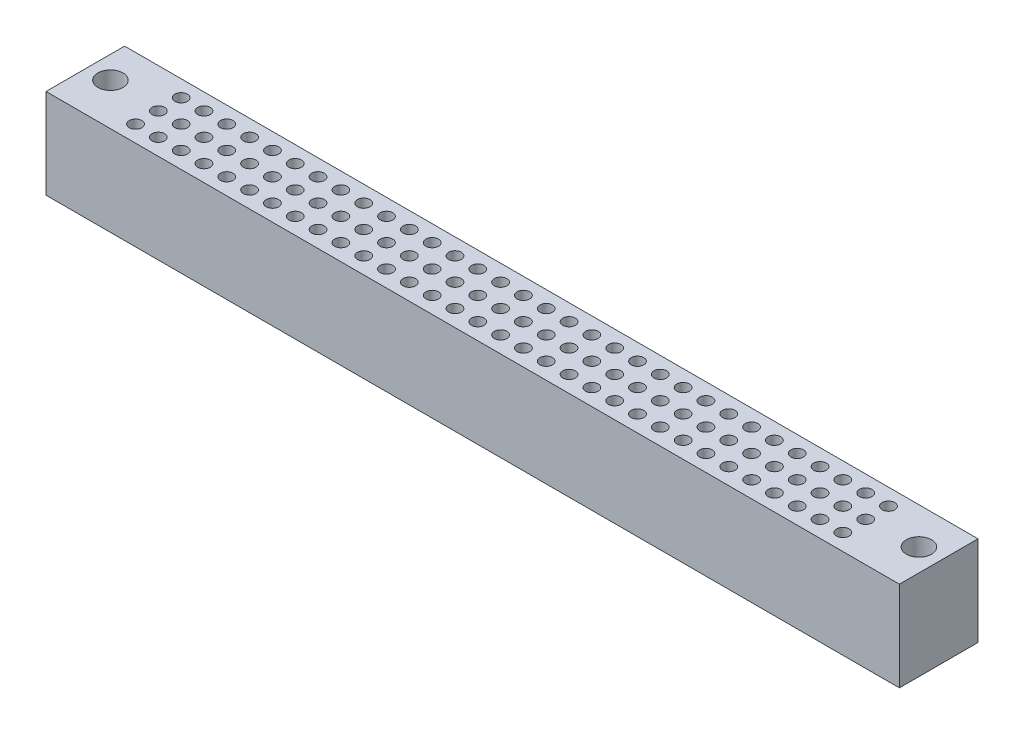
SolidWorks part; units mm, degrees
ref_plane "Front Plane" through (0, 0, 0) normal (0, 0, 1) x (1, 0, 0)
ref_plane "Top Plane" through (0, 0, 0) normal (0, 1, 0) x (1, 0, 0)
ref_plane "Right Plane" through (0, 0, 0) normal (1, 0, 0) x (0, 0, -1)
sketch "Sketch1" plane through (0, 0, 0) normal (0, 1, 0) x (1, 0, 0)
  line L1 (-47.5, -4.375) -> (47.5, -4.375)
  line L2 (-47.5, -4.375) -> (-47.5, 4.375)
  line L3 (-47.5, 4.375) -> (47.5, 4.375)
  line L4 (47.5, -4.375) -> (47.5, 4.375)
  line L5 (-47.5, -4.375) -> (47.5, 4.375) construction
  line L6 (-47.5, 4.375) -> (47.5, -4.375) construction
  point P0 (0, 0)
  dimension "D1" = 95
  dimension "D2" = 8.75
extrude "Boss-Extrude1" add sketch "Sketch1" along normal blind 10
hole_wizard "Ø2.8 (2.8) Diameter Hole1" positions "3DSketch1" profile "Sketch3" hole size "Ø2.8" standard "ISO" end condition through all
sketch3d "3DSketch1"
  line L0 (47.5, 10, -4.375) -> (-47.5, 10, -4.375) construction
  point P0 (-45, 10, -0.3)
  point P2 (45, 10, -0.3)
  dimension "D1" = 4.075
  dimension "D2" = 45
  dimension "D3" = 45
sketch "Sketch3" plane through (-45, 10, -0.3) normal (1, 0, 0) x (0, 0, 1)
  line L0 (0, 0) -> (0, 10)
  line L1 (0, 10) -> (1.4, 10)
  line L2 (1.4, 10) -> (1.4, 0)
  line L5 (1.4, 0) -> (0, 0)
  line L11 (0, -6.35) -> (0, 107.95) construction
  dimension "Thru Hole Dia." = 2.8
  dimension "Thru Hole Depth" = 10
hole_wizard "Ø1.4 (1.4) Diameter Hole1" positions "3DSketch2" profile "Sketch4" hole size "Ø1.4" standard "ISO" end condition through all
sketch3d "3DSketch2"
  line L0 (47.5, 10, -4.375) -> (-47.5, 10, -4.375) construction
  point P0 (-39.37, 10, -2.54)
  point P2 (-39.37, 10, 0)
  point P4 (-39.37, 10, 2.54)
  dimension "D1" = 1.835
  dimension "D2" = 2.54
  dimension "D3" = 2.54
  dimension "D4" = 39.37
sketch "Sketch4" plane through (-39.37, 10, -2.54) normal (1, 0, 0) x (0, 0, 1)
  line L0 (0, 0) -> (0, 10)
  line L1 (0, 10) -> (0.7, 10)
  line L2 (0.7, 10) -> (0.7, 0)
  line L5 (0.7, 0) -> (0, 0)
  line L11 (0, -6.35) -> (0, 107.95) construction
  dimension "Thru Hole Dia." = 1.4
  dimension "Thru Hole Depth" = 10
pattern_linear "LPattern1" count 32 spacing 2.54 along (1, 0, 0) of "Ø1.4 (1.4) Diameter Hole1"
ref_axis "Axis1" through (39.37, 0, 0) along (0, 1, 0)
ref_axis "Axis2" through (-39.37, 0, 0) along (0, 1, 0)
ref_plane "Plane1" through (0, 0, 0) normal (0, 0, -1) x (-1, 0, 0)
ref_plane "Plane2" through (0, 0, 0) normal (-1, 0, 0) x (0, 0, 1)
